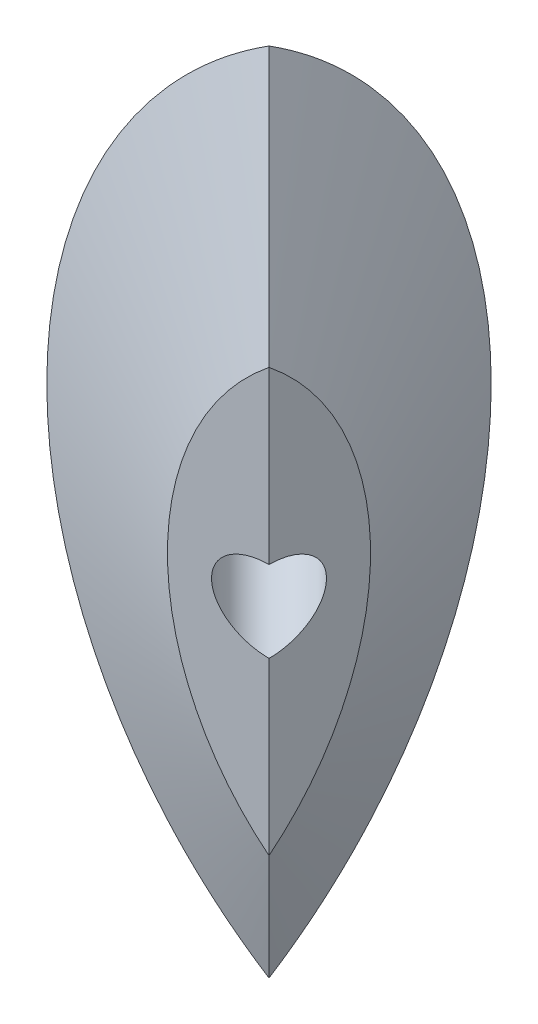
SolidWorks part; units mm, degrees
material "High-leaded brass, UNS C34200"
ref_plane "前视基准面" through (0, 0, 0) normal (0, 0, 1) x (1, 0, 0)
ref_plane "上视基准面" through (0, 0, 0) normal (0, 1, 0) x (1, 0, 0)
ref_plane "右视基准面" through (0, 0, 0) normal (1, 0, 0) x (0, 0, -1)
sketch "草图3" plane through (0, 0, 0) normal (1, 0, 0) x (0, 0, -1)
  line L0 (0, 40) -> (0, -40)
  arc A0 (0, -40) -> (0, 40) centre (0, 0) ccw
  dimension "D1" = 80
revolve "旋转1" add sketch "草图3" angle 360 about L0
sketch "草图4" plane through (0, 0, 0) normal (0, 0, 1) x (1, 0, 0)
  line L0 (-25, 50) -> (25, 50)
  line L1 (25, 50) -> (12.5, 20)
  line L2 (12.5, 20) -> (-12.5, 20)
  line L3 (-12.5, 20) -> (-25, 50)
  line L4 (0, 50.5448) -> (0, -50.4322) construction
  line L5 (-55.2479, 0) -> (81.1192, 0) construction
  dimension "D1" = 50
  dimension "D2" = 25
  dimension "D3" = 25
  dimension "D4" = 12.5
  dimension "D5" = 20
  dimension "D6" = 50
revolve "切除-旋转3" cut sketch "草图4" angle 360 about L5
sketch "草图5" plane through (0, 0, 0) normal (0, 1, 0) x (1, 0, 0)
  line L0 (-48.3452, 0) -> (63.4223, 0) construction
  line L1 (0, 44.0023) -> (0, -58.5878) construction
  line L2 (-50, 25) -> (-50, -25)
  line L3 (-50, -25) -> (-20, -12.5)
  line L4 (-20, -12.5) -> (-20, 12.5)
  line L5 (-20, 12.5) -> (-50, 25)
  dimension "D1" = 50
  dimension "D2" = 20
  dimension "D3" = 50
  dimension "D4" = 25
  dimension "D5" = 25
  dimension "D6" = 12.5
revolve "切除-旋转4" cut sketch "草图5" angle 360 about L1
sketch "草图6" plane through (0, 0, 0) normal (0, 1, 0) x (1, 0, 0)
  line L0 (-20, 12.5) -> (37.5563, 12.5)
  line L1 (37.5563, 12.5) -> (37.5563, -29.2579)
  line L2 (37.5563, -29.2579) -> (31.4866, -38.6469)
  line L3 (31.4866, -38.6469) -> (-34.4266, -38.0779)
  line L4 (-34.4266, -38.0779) -> (-43.7208, -12.1868)
  line L5 (-43.7208, -12.1868) -> (-20, 12.5)
extrude "切除-拉伸1" cut sketch "草图6" against normal through all both and the other way through all
sketch "草图7" plane through (0, 0, 0) normal (0, 1, 0) x (1, 0, 0)
  line L0 (-12.5, 20) -> (-10.1133, 50.0857)
  line L1 (-10.1133, 50.0857) -> (42.8716, 47.2276)
  line L2 (42.8716, 47.2276) -> (40.6347, 5.7583)
  line L3 (40.6347, 5.7583) -> (-0.8794, -1.7267)
  line L4 (-0.8794, -1.7267) -> (-12.5, 12.5)
  line L5 (-12.5, 12.5) -> (-12.5, 20)
extrude "切除-拉伸2" cut sketch "草图7" against normal through all both and the other way through all
ref_plane "基准面4" through (0, 0, 0) normal (0.7071, 0, -0.7071) x (0, 1, 0)
sketch "草图12" plane through (0, 0, 0) normal (0.7071, 0, -0.7071) x (0, 1, 0)
  line L1 (0, 0) -> (3, 0)
  line L2 (0, 0) -> (0, -50.6202)
  line L3 (0, -50.6202) -> (3, -50.6202)
  line L4 (3, 0) -> (3, -50.6202)
  dimension "D1" = 3
revolve "切除-旋转7" cut sketch "草图12" angle 360 about L2
chamfer "倒角1" distance 1 angle 45 1 edges at (-26.0833, 0, -30.3259)
